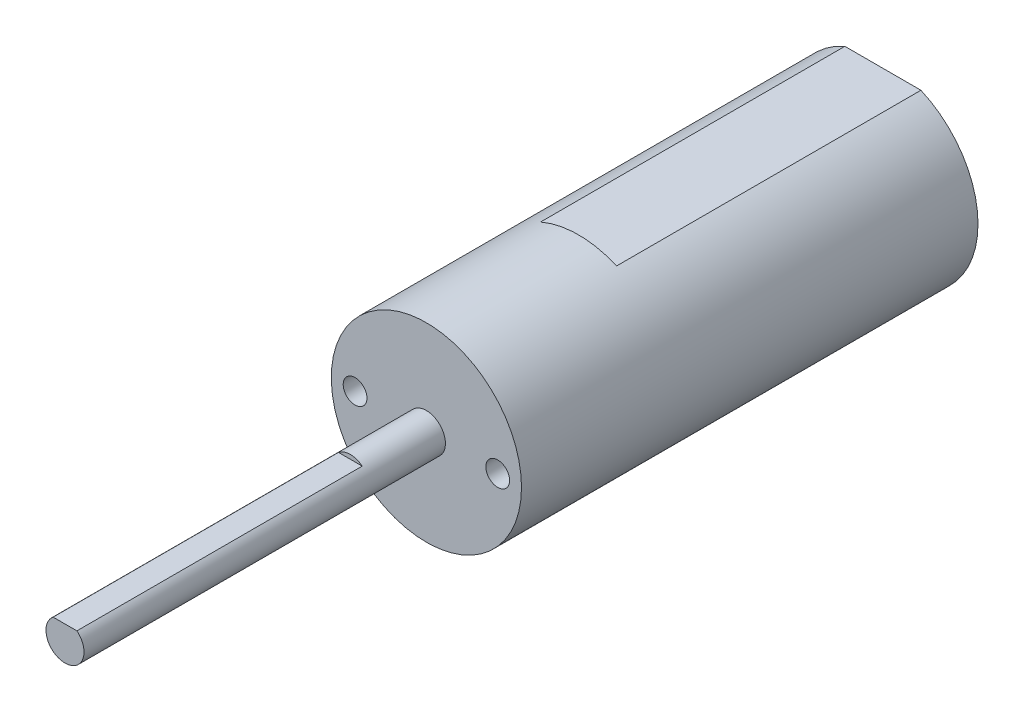
SolidWorks part; units mm, degrees
ref_plane "Front Plane" through (0, 0, 0) normal (0, 0, 1) x (1, 0, 0)
ref_plane "Top Plane" through (0, 0, 0) normal (0, 1, 0) x (1, 0, 0)
ref_plane "Right Plane" through (0, 0, 0) normal (1, 0, 0) x (0, 0, -1)
sketch "Sketch1" plane through (0, 0, 0) normal (0, 0, 1) x (1, 0, 0)
  circle A0 centre (0, 0) radius 10
  dimension "D1" = 20
extrude "Boss-Extrude1" add sketch "Sketch1" along normal blind 32
sketch "Sketch3" plane through (0, 0, 0) normal (0, 0, -1) x (-1, 0, 0)
  line L0 (-4, 9.1652) -> (4, 9.1652)
  line L2 (4, -9.1652) -> (-4, -9.1652)
  circle A0 centre (0, 0) radius 10 construction
  circle A1 centre (0, 0) radius 10
  point P4 (0, 0)
  point P7 (4.3194, 9.019)
  circle M2 centre (0, 0) radius 10
  dimension "D1" = 8
extrude "Cut-Extrude1" cut sketch "Sketch3" against normal blind 32 contours L0 M2 | L2 M2 region at (0, 9.5003, 0) region at (0, -9.5003, 0)
sketch "Sketch4" plane through (0, 0, 32) normal (0, 0, 1) x (1, 0, 0)
  circle A0 centre (0, 0) radius 10
  arc A1 (4, -9.1652) -> (4, 9.1652) centre (0, 0) ccw construction
extrude "Boss-Extrude2" add sketch "Sketch4" along normal blind 16
sketch "Sketch5" plane through (0, 0, 48) normal (0, 0, 1) x (1, 0, 0)
  line L0 (-7.5, 0) -> (0, 0) construction
  line L1 (0, 0) -> (7.5, 0) construction
  circle A0 centre (0, 0) radius 2
  circle A1 centre (-7.5, 0) radius 1.25
  circle A2 centre (7.5, 0) radius 1.25
  dimension "D2" = 2.5
  dimension "D3" = 4
  dimension "D1" = 15
extrude "Cut-Extrude2" cut sketch "Sketch5" against normal blind 6 contours A2 | A1
extrude "Boss-Extrude3" add sketch "Sketch5<3>" along normal blind 38 contours A0 region at (0, 0, 48)
sketch "Sketch5<3>" plane through (0, 0, 48) normal (0, 0, 1) x (1, 0, 0) same geometry as "Sketch5"
sketch "Sketch6" plane through (0, 0, 86) normal (0, 0, 1) x (1, 0, 0)
  line L0 (1.25, 1.5612) -> (-1.25, 1.5612)
  circle A0 centre (0, 0) radius 2 construction
  circle A2 centre (0, 0) radius 2
  circle A3 centre (0, 0) radius 2
  circle M3 centre (0, 0) radius 2
  dimension "D2" = 2.5
  dimension "D1" = 0
extrude "Cut-Extrude3" cut sketch "Sketch6" against normal blind 30 contours L0 M3 region at (0, 1.7385, 86)
